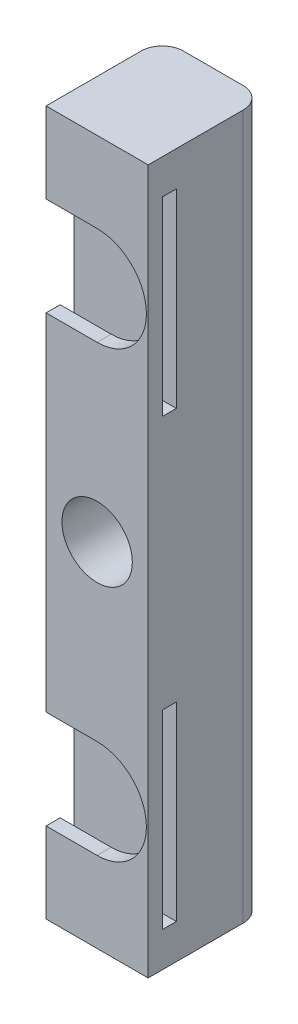
SolidWorks part; units mm, degrees
ref_plane "Front Plane" through (0, 0, 0) normal (1, 0, 0) x (0, 1, 0)
ref_plane "Top Plane" through (0, 0, 0) normal (0, 0, 1) x (0, 1, 0)
ref_plane "Right Plane" through (0, 0, 0) normal (0, 1, 0) x (-1, 0, 0)
sketch "Sketch7" plane through (0, 0, 0) normal (0, 0, 1) x (0, 1, 0)
  line L1 (-50, -7.25) -> (50, -7.25)
  line L2 (-50, -7.25) -> (-50, 7.25)
  line L3 (-50, 7.25) -> (50, 7.25)
  line L4 (50, -7.25) -> (50, 7.25)
  line L5 (-50, -7.25) -> (50, 7.25) construction
  line L6 (-50, 7.25) -> (50, -7.25) construction
  point P0 (0, 0)
  dimension "D1" = 14.5
  dimension "D2" = 100
extrude "Boss-Extrude1" add sketch "Sketch7" along normal blind 16.5
sketch "Sketch8" plane through (0, 0, 16.5) normal (0, 0, 1) x (0, -1, 0)
  circle A0 centre (0, 0) radius 5
  dimension "D1" = 10
extrude "Cut-Extrude2" cut sketch "Sketch8" against normal blind 13
sketch "Sketch9" plane through (0, 0, 16.5) normal (0, 0, 1) x (1, 0, 0)
  line L0 (0, 0) -> (0, -31.55) construction
  line L2 (-13.5, -45.05) -> (13.5, -45.05)
  line L3 (-13.5, -45.05) -> (-13.5, -18.05)
  line L4 (-13.5, -18.05) -> (13.5, -18.05)
  line L5 (13.5, -45.05) -> (13.5, -18.05)
  line L6 (-13.5, -45.05) -> (13.5, -18.05) construction
  line L7 (-13.5, -18.05) -> (13.5, -45.05) construction
  dimension "D1" = 31.55
  dimension "D2" = 27
extrude "Cut-Extrude3" cut sketch "Sketch9" against normal blind 2 from offset 2 offset against normal yes
sketch "Sketch10" plane through (0, 0, 16.5) normal (0, 0, 1) x (1, 0, 0)
  line L0 (0, 0) -> (0, -31.55) construction
  line L1 (0, -24.55) -> (-7.25, -24.55)
  line L2 (-7.25, 50) -> (-7.25, -50) construction
  line L3 (-7.25, -24.55) -> (-7.25, -38.55)
  line L4 (0, -38.55) -> (-7.25, -38.55)
  arc A0 (0, -38.55) -> (0, -24.55) centre (0, -31.55) ccw
  point P3 (0, 0)
  dimension "D2" = 14
  dimension "D1" = 31.55
extrude "Cut-Extrude4" cut sketch "Sketch10" against normal blind 2
mirror "Mirror1" about plane through (0, 0, 0) normal (0, 1, 0) of "Cut-Extrude3"
mirror "Mirror2" about plane through (0, 0, 0) normal (0, 1, 0) of "Cut-Extrude4"
fillet "Fillet1" radius 3 1 edges at (-7.25, 0, 0) type face fillet first side face at (-7.25, 0, 13.25) second side face at (0, 0, 0)
fillet "Fillet2" radius 3 1 edges at (7.25, 0, 0) type face fillet first side face at (7.25, 31.55, 13.5) second side face at (1.5, 0, 0)
